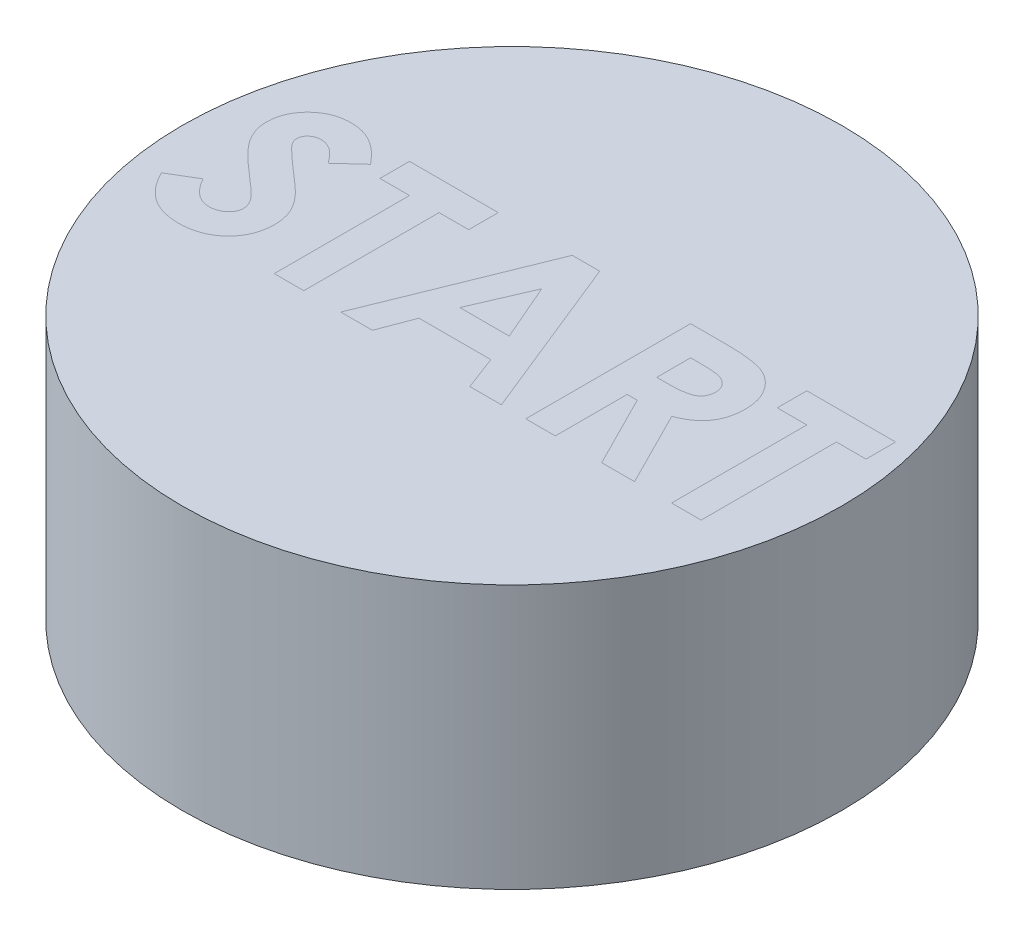
SolidWorks part; units mm, degrees
ref_plane "Front Plane" through (0, 0, 0) normal (0, 0, 1) x (1, 0, 0)
ref_plane "Top Plane" through (0, 0, 0) normal (0, 1, 0) x (1, 0, 0)
ref_plane "Right Plane" through (0, 0, 0) normal (1, 0, 0) x (0, 0, -1)
sketch "Sketch3" plane through (0, 0, 0) normal (0, 1, 0) x (1, 0, 0)
  line L1 (1.075, -1.575) -> (-1.075, -1.575)
  line L2 (1.075, -1.575) -> (1.075, 1.575)
  line L3 (1.075, 1.575) -> (-1.075, 1.575)
  line L4 (-1.075, -1.575) -> (-1.075, 1.575)
  line L5 (1.075, -1.575) -> (-1.075, 1.575) construction
  line L6 (1.075, 1.575) -> (-1.075, -1.575) construction
  circle A0 centre (0, 0) radius 10
  point P0 (0, 0)
  dimension "D3" = 20
  dimension "D1" = 2.15
  dimension "D2" = 3.15
extrude "Boss-Extrude1" add sketch "Sketch3" against normal blind 3
sketch "Sketch4" plane through (0, 0, 0) normal (0, 1, 0) x (1, 0, 0)
  circle A1 centre (0, 0) radius 10
  circle A2 centre (0, 0) radius 10
  dimension "D1" = 0
extrude "Boss-Extrude2" add sketch "Sketch4" along normal blind 5
sketch "Sketch5" plane through (0, 0, 0) normal (0, 1, 0) x (1, 0, 0)
  line L0 (-9.6825, -2.5) -> (9.6825, -2.5) construction
  line L1 (9.6825, -2.5) -> (9.6825, 2.5) construction
  circle A0 centre (0, 0) radius 10 construction
  text T0 "START" font "Century Gothic" height 5
  dimension "D1" = 5
extrude "Cut-Extrude1" cut sketch "Sketch5" against normal blind 0.4 and the other way through all from surface starting at face at (0, 5, 10)
extrude "Boss-Extrude3" add sketch "Sketch5<2>" against normal blind 0.4 from surface separate body starting at face at (-7.4353, 5, -0.1249)
sketch "Sketch5<2>" plane through (0, 0, 0) normal (0, 1, 0) x (1, 0, 0) same geometry as "Sketch5"
equation "\"m3 hole\"= 3.2"
equation "\"m4 hole\"= 4.2"
equation "\"m5 hole\"= 5.2"
equation "\"m6 hole\"= 6.2"
equation "\"m8 hole\"= 8.2"
equation "\"m3 tapped\"= 2.5"
equation "\"m4 tapped\"= 3.3"
equation "\"m5 tapped\"= 4.2"
equation "\"m6 tapped\"= 5"
equation "\"m8 tapped\"= 6.8"
